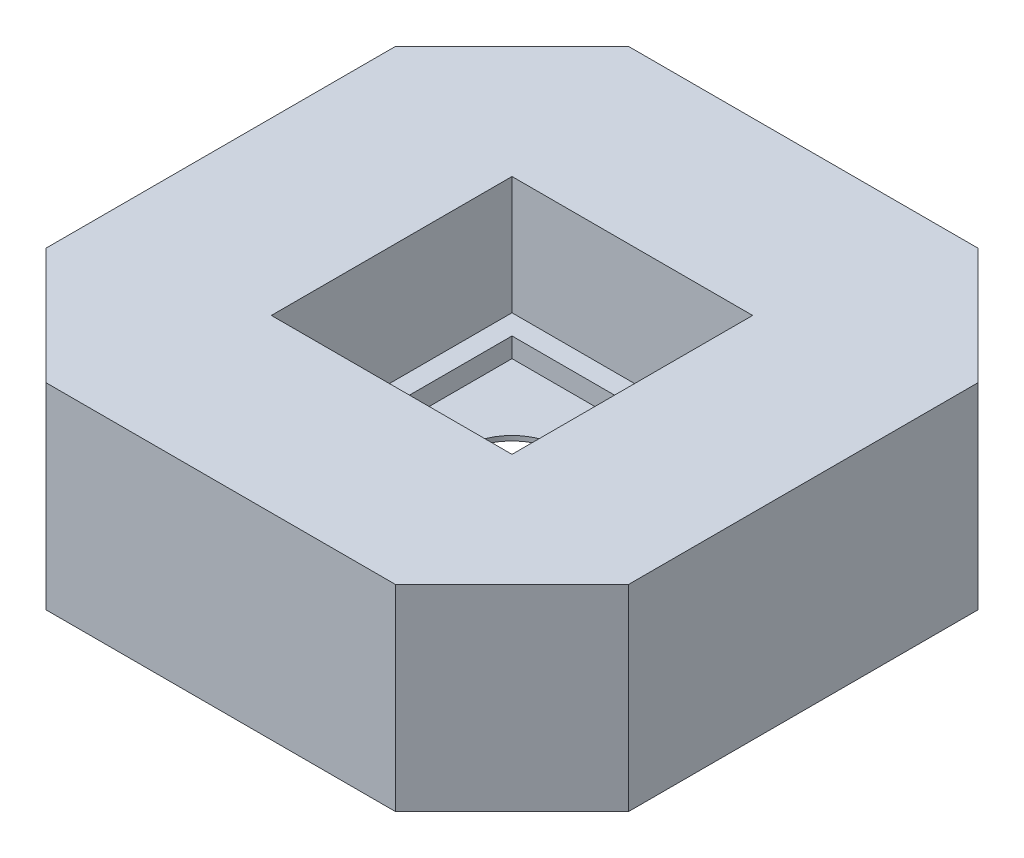
SolidWorks part; units mm, degrees
ref_plane "前视基准面" through (0, 0, 0) normal (0, 0, 1) x (1, 0, 0)
ref_plane "上视基准面" through (0, 0, 0) normal (0, 1, 0) x (1, 0, 0)
ref_plane "右视基准面" through (0, 0, 0) normal (1, 0, 0) x (0, 0, -1)
sketch "草图1" plane through (0, 0, 0) normal (0, 1, 0) x (1, 0, 0)
  line L0 (-305, 183) -> (-183, 305)
  line L1 (-183, -305) -> (183, -305)
  line L2 (-305, -183) -> (-305, 183)
  line L3 (-183, 305) -> (183, 305)
  line L4 (305, -183) -> (305, 183)
  line L5 (-305, -305) -> (305, 305) construction
  line L6 (-305, 305) -> (305, -305) construction
  line L7 (-305, -183) -> (-183, -305)
  line L8 (183, -305) -> (305, -183)
  line L9 (183, 305) -> (305, 183)
  point P0 (0, 0)
  dimension "D1" = 610
  dimension "D2" = 610
extrude "凸台-拉伸1" add sketch "草图1" along normal blind 206
sketch "草图2" plane through (0, 206, 0) normal (0, 1, 0) x (1, 0, 0)
  line L1 (-126, -126) -> (126, -126)
  line L2 (-126, -126) -> (-126, 126)
  line L3 (-126, 126) -> (126, 126)
  line L4 (126, -126) -> (126, 126)
  line L5 (-126, -126) -> (126, 126) construction
  line L6 (-126, 126) -> (126, -126) construction
  point P0 (0, 0)
  dimension "D1" = 252
extrude "切除-拉伸1" cut sketch "草图2" against normal blind 123.6
sketch "草图3" plane through (0, 206, 0) normal (0, 1, 0) x (1, 0, 0)
  line L1 (-105, -105) -> (105, -105)
  line L2 (-105, -105) -> (-105, 105)
  line L3 (-105, 105) -> (105, 105)
  line L4 (105, -105) -> (105, 105)
  line L5 (-105, -105) -> (105, 105) construction
  line L6 (-105, 105) -> (105, -105) construction
  point P0 (0, 0)
  dimension "D1" = 210
extrude "切除-拉伸2" cut sketch "草图3" against normal blind 144.2
shell "抽壳1" thickness 5 removed face at (0, 0, 0)
sketch "草图4" plane through (0, 61.8, 0) normal (0, 1, 0) x (1, 0, 0)
  circle A0 centre (0, 0) radius 50
  dimension "D1" = 100
extrude "切除-拉伸3" cut sketch "草图4" against normal through all
ref_plane "基准面1" through (0, 0, 91.5) normal (0, 0, 1) x (1, 0, 0)
sketch "草图5" plane through (0, 0, 91.5) normal (0, 0, 1) x (1, 0, 0)
  line L0 (-131, 82.4) -> (-300, 112.1993)
  line L1 (-131, 77.4) -> (-131, 201) construction
  line L2 (-300, 201) -> (-300, 0) construction
  line L3 (131, 77.4) -> (-131, 77.4) construction
  dimension "D1" = 80
  dimension "D2" = 5
rib "筋1" sketch "草图5" sketch "草图5" thickness 10 extrusion direction parallel to sketch draft on no parameters "D1"=10
mirror "镜向1" about plane through (0, 0, 0) normal (0, 0, 1) of "筋1"
pattern_circular "阵列(圆周)1" count 4 over 360 about axis through (0, 0, 0) along (0, 1, 0) of "镜向1" reverse direction yes
